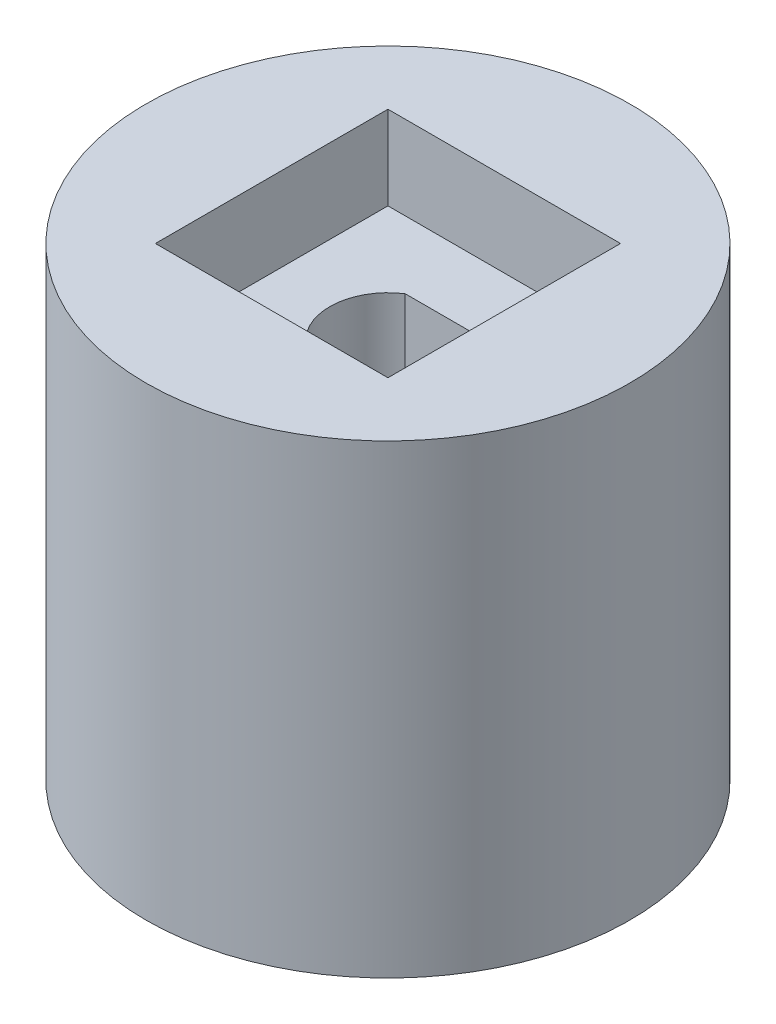
SolidWorks part; units mm, degrees
material "PBT General Purpose"
ref_plane "Front Plane" through (0, 0, 0) normal (0, 0, 1) x (1, 0, 0)
ref_plane "Top Plane" through (0, 0, 0) normal (0, 1, 0) x (1, 0, 0)
ref_plane "Right Plane" through (0, 0, 0) normal (1, 0, 0) x (0, 0, -1)
sketch "Sketch1" plane through (0, 0, 0) normal (0, 1, 0) x (1, 0, 0)
  line L0 (0, -3.175) -> (5.0633, -3.175) construction
  line L1 (0, -3.0734) -> (0, 3.0734) construction
  line L2 (0, -3.175) -> (-5.0664, -3.175) construction
  line L3 (0, 2.667) -> (-1.7227, 2.667)
  line L6 (0, 2.667) -> (1.7227, 2.667)
  circle A0 centre (0, 0) radius 13.208
  circle A1 centre (0, 0) radius 3.175
  point P8 (0, 2.667)
extrude "Boss-Extrude4" add sketch "Sketch1" along normal blind 25.4 contours A0 A1 | L6 A1 L3 | L3 A1 L6 region at (0, 0, 0.1118) region at (0, 0, -2.8717) region at (-12.8344, 0, 0)
extrude "Cut-Extrude3" cut sketch "Sketch1<6>" along normal through all contours L3 A1 L6 region at (0, 0, 0.1118)
sketch "Sketch1<6>" plane through (0, 0, 0) normal (0, 1, 0) x (1, 0, 0) same geometry as "Sketch1"
extrude "Cut-Extrude4" cut sketch "Sketch1<7>" along normal blind 4.064 contours L6 A1 L3 region at (0, 0, -2.8717)
sketch "Sketch1<7>" plane through (0, 0, 0) normal (0, 1, 0) x (1, 0, 0) same geometry as "Sketch1"
sketch "Sketch2" plane through (0, 25.4, 0) normal (0, 1, 0) x (1, 0, 0)
  line L1 (-6.35, -6.35) -> (6.35, -6.35)
  line L2 (-6.35, -6.35) -> (-6.35, 6.35)
  line L3 (-6.35, 6.35) -> (6.35, 6.35)
  line L4 (6.35, -6.35) -> (6.35, 6.35)
  line L5 (-6.35, -6.35) -> (6.35, 6.35) construction
  line L6 (-6.35, 6.35) -> (6.35, -6.35) construction
  point P0 (0, 0)
extrude "Cut-Extrude5" cut sketch "Sketch2" against normal blind 4.572
